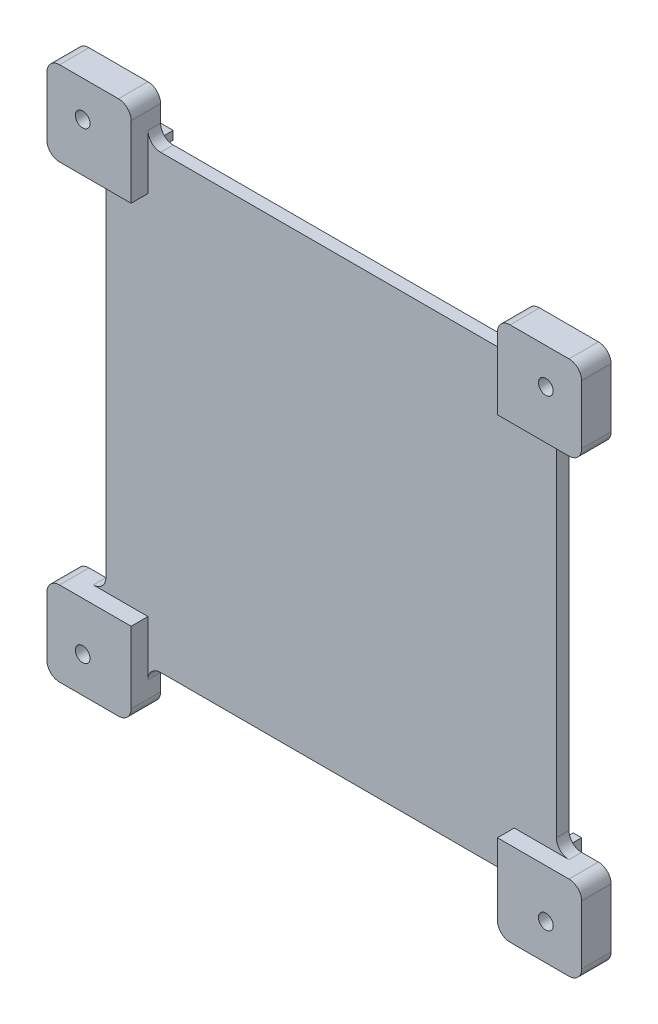
SolidWorks part; units mm, degrees
ref_plane "Front Plane" through (0, 0, 0) normal (0, 0, 1) x (1, 0, 0)
ref_plane "Top Plane" through (0, 0, 0) normal (0, 1, 0) x (1, 0, 0)
ref_plane "Right Plane" through (0, 0, 0) normal (1, 0, 0) x (0, 0, -1)
sketch "Sketch1" plane through (0, 0, 0) normal (0, 0, 1) x (1, 0, 0)
  line L1 (0, 0) -> (107, 0)
  line L2 (0, 0) -> (0, 107)
  line L3 (0, 107) -> (107, 107)
  line L4 (107, 0) -> (107, 107)
  dimension "D1" = 107
  dimension "D2" = 107
extrude "Boss-Extrude1" add sketch "Sketch1" along normal blind 6
shell "Shell6" thickness 2 removed face at (53.5, 53.5, 0)
sketch "Sketch2" plane through (0, 105, 0) normal (0, -1, 0) x (1, 0, 0)
  line L0 (0, 0) -> (107, 0) construction
  line L1 (10, 3) -> (99, 3)
  line L2 (10, 3) -> (10, 0)
  line L3 (10, 0) -> (99, 0)
  line L4 (99, 3) -> (99, 0)
  line L5 (0, 6) -> (0, 0) construction
  line L6 (107, 6) -> (107, 0) construction
  line L7 (0, 6) -> (107, 6) construction
  point P10 (107, 3)
  dimension "D1" = 10
  dimension "D2" = 8
  dimension "D3" = 3
extrude "Cut-Extrude1" cut sketch "Sketch2" against normal blind 105 and the other way through all
sketch "Sketch3" plane through (107, 0, 0) normal (1, 0, 0) x (0, 0, -1)
  line L0 (-6, 107) -> (0, 107) construction
  line L1 (-3, 97) -> (1.8237, 97)
  line L2 (-3, 97) -> (-3, 10)
  line L3 (-3, 10) -> (1.8237, 10)
  line L4 (1.8237, 97) -> (1.8237, 10)
  line L5 (-6, 0) -> (0, 0) construction
  line L6 (-6, 0) -> (-6, 107) construction
  dimension "D1" = 10
  dimension "D2" = 10
  dimension "D3" = 3
extrude "Cut-Extrude2" cut sketch "Sketch3" against normal through all and the other way through all
sketch "Sketch4" plane through (0, 0, 6) normal (0, 0, 1) x (1, 0, 0)
  line L0 (10, 107) -> (10, 97)
  line L1 (107, 107) -> (0, 107) construction
  line L2 (10, 97) -> (-10, 97)
  line L3 (-10, 97) -> (-10, 117)
  line L4 (-10, 117) -> (10, 117)
  line L5 (10, 117) -> (10, 107)
  line L6 (0, 107) -> (0, 0) construction
  line L7 (53.5, 107) -> (53.5, 82.782) construction
  line L8 (0, 53.5) -> (44.2362, 53.5) construction
  line L9 (97, 97) -> (117, 97)
  line L10 (97, 117) -> (97, 107)
  line L11 (97, 107) -> (97, 97)
  line L12 (117, 97) -> (117, 117)
  line L13 (117, 117) -> (97, 117)
  line L14 (117, -10) -> (97, -10)
  line L15 (117, 10) -> (117, -10)
  line L16 (97, 10) -> (117, 10)
  line L17 (97, 0) -> (97, 10)
  line L18 (10, 0) -> (10, 10)
  line L19 (-10, 10) -> (-10, -10)
  line L20 (10, 10) -> (-10, 10)
  line L21 (97, -10) -> (97, 0)
  line L22 (10, -10) -> (10, 0)
  line L23 (-10, -10) -> (10, -10)
  circle A0 centre (-1.5, 108.5) radius 1.75
  circle A1 centre (108.5, 108.5) radius 1.75
  circle A2 centre (108.5, -1.5) radius 1.75
  circle A3 centre (-1.5, -1.5) radius 1.75
  dimension "D5" = 3.5
  dimension "D1" = 20
  dimension "D2" = 20
  dimension "D3" = 10
  dimension "D4" = 10
  dimension "D6" = 110
  dimension "D7" = 110
extrude "Boss-Extrude2" add sketch "Sketch4" along normal blind 7
sketch "Sketch5" plane through (0, 0, 6) normal (0, 0, -1) x (-1, 0, 0)
  line L0 (-107, 97) -> (-117, 97)
  line L1 (-117, 97) -> (-117, 117)
  line L2 (-117, 117) -> (-97, 117)
  line L3 (-97, 117) -> (-97, 107)
  line L4 (-97, 107) -> (-107, 107)
  line L5 (-107, 107) -> (-107, 97)
  line L6 (-53.5, 90.8128) -> (-53.5, 77.3263) construction
  line L7 (-97, 107) -> (-10, 107) construction
  line L8 (-89.4449, 53.5) -> (-73.224, 53.5) construction
  line L9 (-107, 10) -> (-107, 97) construction
  line L10 (10, 97) -> (10, 117)
  line L11 (0, 97) -> (10, 97)
  line L12 (0, 107) -> (0, 97)
  line L13 (-10, 107) -> (0, 107)
  line L14 (-10, 117) -> (-10, 107)
  line L15 (10, 117) -> (-10, 117)
  line L16 (10, 10) -> (10, -10)
  line L17 (0, 10) -> (10, 10)
  line L18 (0, 0) -> (0, 10)
  line L19 (-10, 0) -> (0, 0)
  line L20 (10, -10) -> (-10, -10)
  line L21 (-10, -10) -> (-10, 0)
  line L22 (-117, 10) -> (-117, -10)
  line L23 (-117, -10) -> (-97, -10)
  line L24 (-97, -10) -> (-97, 0)
  line L25 (-97, 0) -> (-107, 0)
  line L26 (-107, 0) -> (-107, 10)
  line L27 (-107, 10) -> (-117, 10)
  circle A0 centre (-108.5, 108.5) radius 1.75
  circle A1 centre (1.5, 108.5) radius 1.75
  circle A2 centre (1.5, -1.5) radius 1.75
  circle A3 centre (-108.5, -1.5) radius 1.75
  point P19 (-53.5, 107)
  point P24 (-107, 53.5)
  dimension "D1" = 3.5
extrude "Boss-Extrude3" add sketch "Sketch5" along normal blind 3
sketch "Sketch6" plane through (0, 0, 13) normal (0, 0, 1) x (1, 0, 0)
  line L1 (117, 117) -> (-10, 117)
  line L2 (117, 117) -> (117, -10)
  line L3 (117, -10) -> (-10, -10)
  line L4 (-10, 117) -> (-10, -10)
extrude "Cut-Extrude3" cut sketch "Sketch6" against normal blind 3
fillet "Fillet2" radius 3 20 edges at (0, 10, 4.5) (-10, 10, 6.5) (0, 97, 4.5) (-10, 97, 6.5) (-10, 117, 6.5) (10, 117, 6.5) (10, 107, 4.5) (97, 107, 4.5) (97, 117, 6.5) (117, 117, 6.5) (117, 97, 6.5) (107, 97, 4.5) (107, 10, 4.5) (117, 10, 6.5) (117, -10, 6.5) (97, -10, 6.5) (97, 0, 4.5) (10, 0, 4.5) (10, -10, 6.5) (-10, -10, 6.5)
